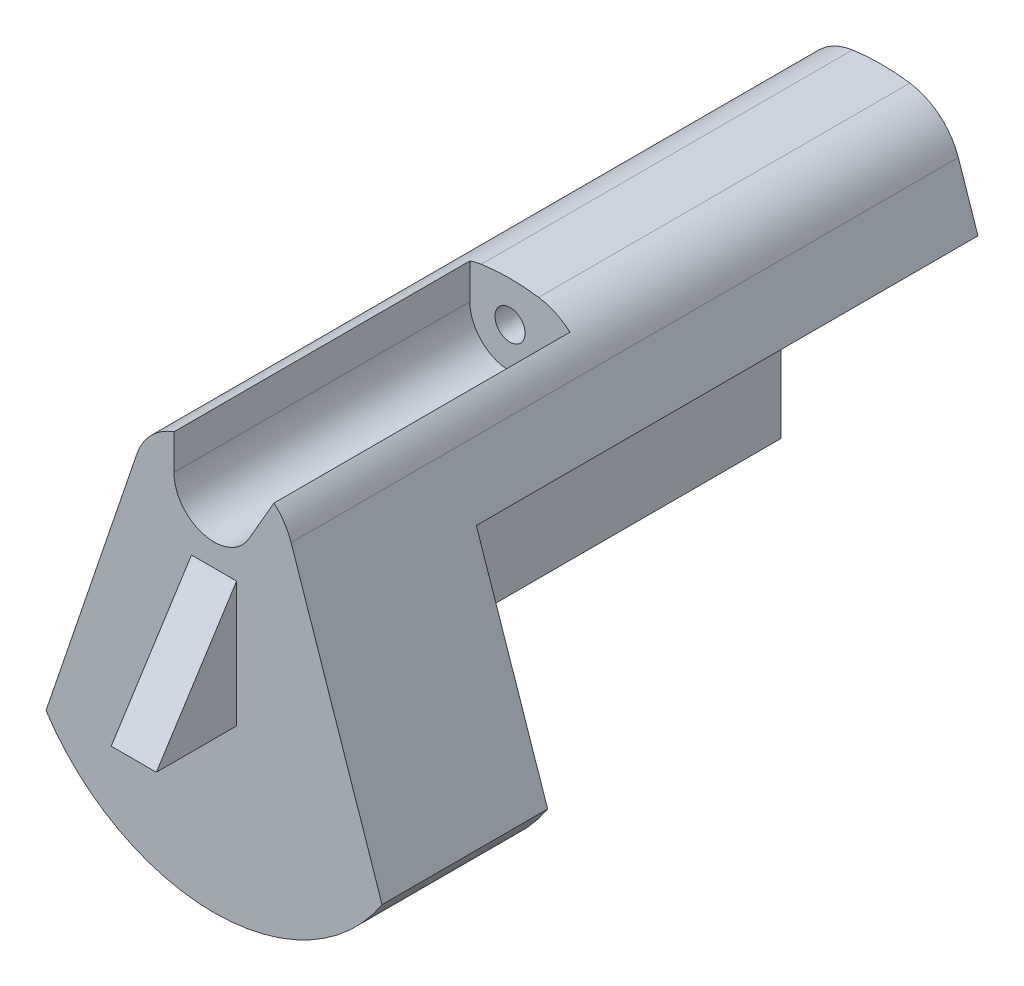
SolidWorks part; units mm, degrees
ref_plane "前视基准面" through (0, 0, 0) normal (0, 0, 1) x (1, 0, 0)
ref_plane "上视基准面" through (0, 0, 0) normal (0, 1, 0) x (1, 0, 0)
ref_plane "右视基准面" through (0, 0, 0) normal (1, 0, 0) x (0, 0, -1)
other "Configuration Table"
sketch "草图1" plane through (0, 0, 0) normal (0, 0, 1) x (1, 0, 0)
  line L0 (-16.75, -10.9287) -> (-7.6819, 15.785)
  line L1 (0, 16) -> (0, 0) construction
  line L2 (16.75, -10.9287) -> (7.6819, 15.785)
  line L3 (0, 10) -> (9.6456, 10)
  line L4 (-10, 0) -> (-10, -17.3205)
  circle A0 centre (0, 0) radius 8.25
  arc A1 (-16.75, -10.9287) -> (16.75, -10.9287) centre (0, 0) ccw
  circle A2 centre (0, 16) radius 1.5
  arc A3 (2.8576, 19.7948) -> (-2.8576, 19.7948) centre (0, 0) ccw
  arc A4 (7.6819, 15.785) -> (2.8576, 19.7948) centre (2.0003, 13.8564) ccw
  arc A5 (-7.6819, 15.785) -> (-2.8576, 19.7948) centre (-2.0003, 13.8564) cw
  arc A6 (0, 10) -> (-10, 0) centre (0, 0) ccw
  point P11 (6.6357, 18.8671)
  point P14 (-6.6357, 18.8671)
  dimension "D1" = 16.5
  dimension "D2" = 40
  dimension "D4" = 3
  dimension "D7" = 6
  dimension "D8" = 20
  dimension "D3" = 16
  dimension "D5" = 33.5
  dimension "D6" = 37.5
extrude "凸台-拉伸1" add sketch "草图1" along normal blind 66.5 contours A2 L3 L2 A4 A3 A5 L0 A1 L4 A6 | L3 A0 A6 L4 A1 L2 | A0 region at (-11.7831, 2.2812, 0) region at (2.9532, -7.8633, 0) region at (0, 0, 0)
sketch "草图2" plane through (0, 0, 66.5) normal (0, 0, 1) x (1, 0, 0)
  line L0 (3.4641, 14) -> (5.9758, 18.3503)
  line L1 (-4, 16) -> (-4, 19.5133)
  line L2 (0, 16) -> (-1.5, 16) construction
  arc A0 (-4, 16) -> (3.4641, 14) centre (0, 16) ccw
  arc A1 (7.6819, 15.785) -> (2.8576, 19.7948) centre (2.0003, 13.8564) ccw construction
  arc A2 (-2.8576, 19.7948) -> (-7.6819, 15.785) centre (-2.0003, 13.8564) ccw construction
  circle A3 centre (0, 16) radius 1.5 construction
  arc A4 (2.8576, 19.7948) -> (-2.8576, 19.7948) centre (0, 0) ccw construction
  arc A5 (5.9758, 18.3503) -> (2.8576, 19.7948) centre (2.0003, 13.8564) ccw
  arc A6 (-2.8576, 19.7948) -> (-4, 19.5133) centre (-2.0003, 13.8564) ccw
  arc A7 (2.8576, 19.7948) -> (-2.8576, 19.7948) centre (0, 0) ccw
  dimension "D1" = 8
  dimension "D2" = 120
extrude "切除-拉伸1" cut sketch "草图2" against normal blind 29.5 and the other way through all
extrude "切除-拉伸2" cut sketch "草图1<3>" along normal blind 50 contours L3 A0 A6 L4 A1 L2 | A0 region at (2.9532, -7.8633, 0) region at (0, 0, 0)
sketch "草图1<3>" plane through (0, 0, 0) normal (0, 0, 1) x (1, 0, 0) same geometry as "草图1"
extrude "切除-拉伸3" cut sketch "草图1<4>" along normal blind 60 contours A0 region at (0, 0, 0)
sketch "草图1<4>" plane through (0, 0, 0) normal (0, 0, 1) x (1, 0, 0) same geometry as "草图1"
sketch "草图3" plane through (0, 0, 0) normal (1, 0, 0) x (0, 0, -1)
  line L0 (-66.5, 9.75) -> (-66.5, -2.75)
  line L1 (-66.5, -10.9287) -> (-66.5, 15.785) construction
  line L2 (-66.5, -2.75) -> (-74.5, -2.75)
  line L3 (-74.5, -2.75) -> (-66.5, 9.75)
  line L4 (-37, 16) -> (-66.5, 16) construction
  dimension "D1" = 18.75
  dimension "D2" = 8
  dimension "D3" = 12.5
extrude "凸台-拉伸2" add sketch "草图3" along normal mid plane 4.5
